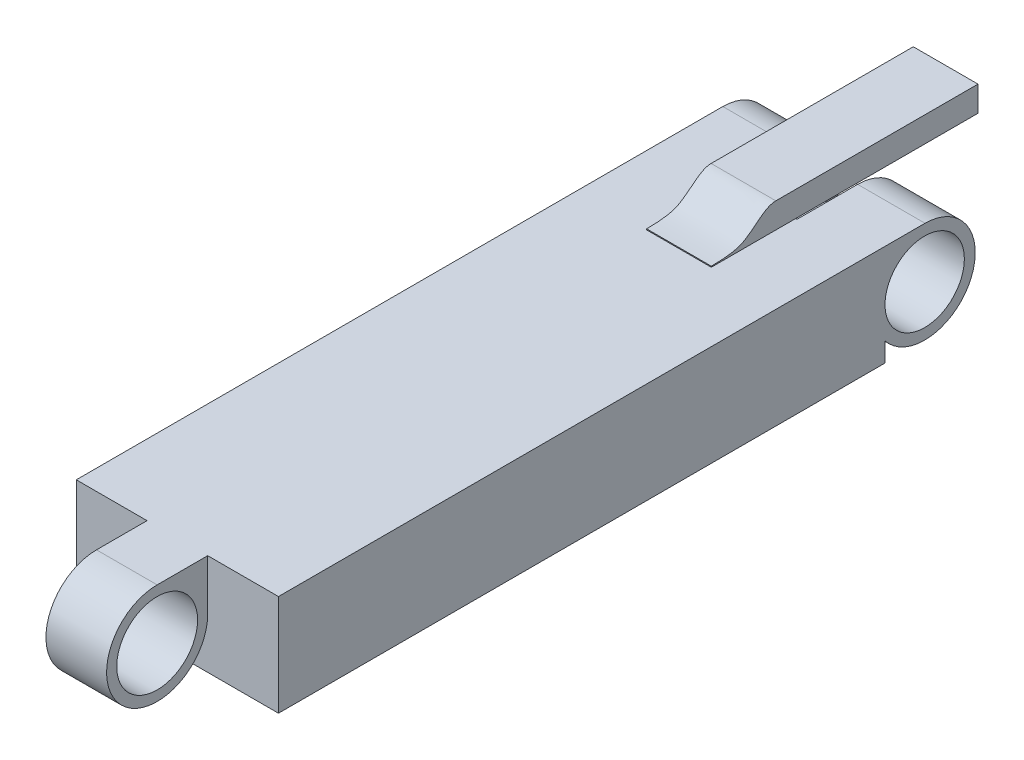
SolidWorks part; units mm, degrees
ref_plane "Front Plane" through (0, 0, 0) normal (0, 0, 1) x (1, 0, 0)
ref_plane "Top Plane" through (0, 0, 0) normal (0, 1, 0) x (1, 0, 0)
ref_plane "Right Plane" through (0, 0, 0) normal (1, 0, 0) x (0, 0, -1)
sketch "Sketch3" plane through (0, 0, 0) normal (1, 0, 0) x (0, 0, -1)
  line L0 (30, 2.5) -> (31.9626, 2.5) construction
  line L1 (0, 0) -> (30, 0)
  line L2 (0, 0) -> (0, 5)
  line L3 (0, 5) -> (30, 5)
  line L4 (30, 0) -> (30, 2.5)
  line L5 (30, 5) -> (31.9789, 5)
  line L6 (30, 5) -> (31.9789, 5)
  line L7 (31.9789, 5) -> (31.9626, 2.5)
  line L8 (31.9626, 2.5) -> (30, 2.5)
  dimension "D1" = 30
  dimension "D2" = 5
extrude "Boss-Extrude1" add sketch "Sketch3" along normal blind 10 contours L8 L7 L5 L3 L2 L1 L4 region at (0, 2.5398, -15.5084)
sketch "Sketch4" plane through (0, 0, 0) normal (1, 0, 0) x (0, 0, -1)
  circle A0 centre (31.9626, 2.5) radius 1.9626
sketch "Sketch6" plane through (0, 0, 0) normal (-1, 0, 0) x (0, 0, 1)
  circle A0 centre (-31.9626, 2.5) radius 2.5
  circle A1 centre (-31.9626, 2.5) radius 1.9626
extrude "Cut-Extrude2" cut sketch "Sketch4" along normal blind 10
extrude "Boss-Extrude2" add sketch "Sketch6" against normal blind 3.3333
sketch "Sketch7" plane through (10, 0, 0) normal (1, 0, 0) x (0, 0, -1)
  circle A0 centre (31.9626, 2.5) radius 1.9626
  circle A1 centre (31.9626, 2.5) radius 2.5
extrude "Boss-Extrude3" add sketch "Sketch7" against normal blind 3.3333
sketch "Sketch8" plane through (3.3333, 0, 0) normal (1, 0, 0) x (0, 0, -1)
  circle A0 centre (31.9626, 2.5) radius 1.9626
  circle A1 centre (31.9626, 2.5) radius 2.5
sketch "Sketch9" plane through (0, -0.2083, -31.945) normal (0, -0.0065, -1) x (-1, 0, 0)
  line L1 (-6.6667, 5.2084) -> (-3.3333, 5.2084)
  line L2 (-6.6667, 5.2084) -> (-6.6667, 0.2084)
  line L3 (-6.6667, 0.2084) -> (-3.3333, 0.2084)
  line L4 (-3.3333, 5.2084) -> (-3.3333, 0.2084)
extrude "Cut-Extrude7" cut sketch "Sketch9" against normal blind 3
sketch "Sketch10" plane through (0, 0.2084, -0.0014) normal (0, 1, -0.0065) x (1, 0, 0)
  line L1 (3.3333, 29.983) -> (6.6667, 29.983)
  line L2 (3.3333, 29.983) -> (3.3333, 28.9457)
  line L3 (3.3333, 28.9457) -> (6.6667, 28.9457)
  line L4 (6.6667, 29.983) -> (6.6667, 28.9457)
extrude "Cut-Extrude8" cut sketch "Sketch10" against normal through all
sketch "Sketch11" plane through (0, 5, 0) normal (0, 1, 0) x (1, 0, 0)
  line L0 (10, 0) -> (5, 0) construction
  line L1 (10, 0) -> (0, 0) construction
  line L2 (5, 0) -> (5, 6.4174) construction
ref_plane "Plane1" through (5, 0, 0) normal (1, 0, 0) x (0, 0, -1)
sketch "Sketch12" plane through (5, 0, 0) normal (1, 0, 0) x (0, 0, -1)
  line L0 (0, 2.5) -> (-2.5, 2.5) construction
  line L1 (0, 0) -> (0, 5) construction
  line L2 (-2.5, 5) -> (0, 5)
  line L3 (0, 5) -> (6.4174, 5) construction
  line L4 (0, 5) -> (0, 2.5)
  arc A0 (-2.5, 5) -> (0, 2.5) centre (-2.5, 2.5) ccw
  circle A1 centre (-2.5, 2.5) radius 2
extrude "Boss-Extrude4" add sketch "Sketch12" along normal blind 1.5 and the other way blind 1.5
sketch "Sketch13" plane through (5, 0, 0) normal (1, 0, 0) x (0, 0, -1)
  line L0 (30, 0.9514) -> (30, 5) construction
  line L1 (0, 5) -> (31.9789, 5) construction
  line L2 (30, 5) -> (28, 5) construction
  line L3 (24.8091, 5) -> (28, 5)
  line L4 (28, 5) -> (38, 5)
  line L6 (28, 6.25) -> (38, 6.25)
  line L7 (38, 5) -> (38, 6.25)
  line L8 (24.8091, 5) -> (24.8091, 5.047)
  spline S0 degree 3 poles (28, 6.25) (27.5701, 6.25) (27.108, 5.7874) (26.4447, 5.3239) (26.114, 5.047) (24.8091, 5.047) knots 0 0 0 0 0.435998 0.535998 1 1 1 1
  point P10 (26.7894, 5.5653)
  point P12 (0, 0)
  point P13 (0, 0)
  point P14 (0, 0)
  point P15 (0, 0)
  point P16 (0, 0)
  point P18 (0, 0)
  point P20 (0, 0)
  dimension "D1" = 10
  dimension "D2" = 1.25
  dimension "D3" = 0.047
  dimension "D4" = 24.8091
  dimension "D5" = 26.7894
  dimension "D6" = 28
  dimension "D7" = 5.5653
extrude "Boss-Extrude9" add sketch "Sketch13" along normal blind 1.6 and the other way blind 1.6
